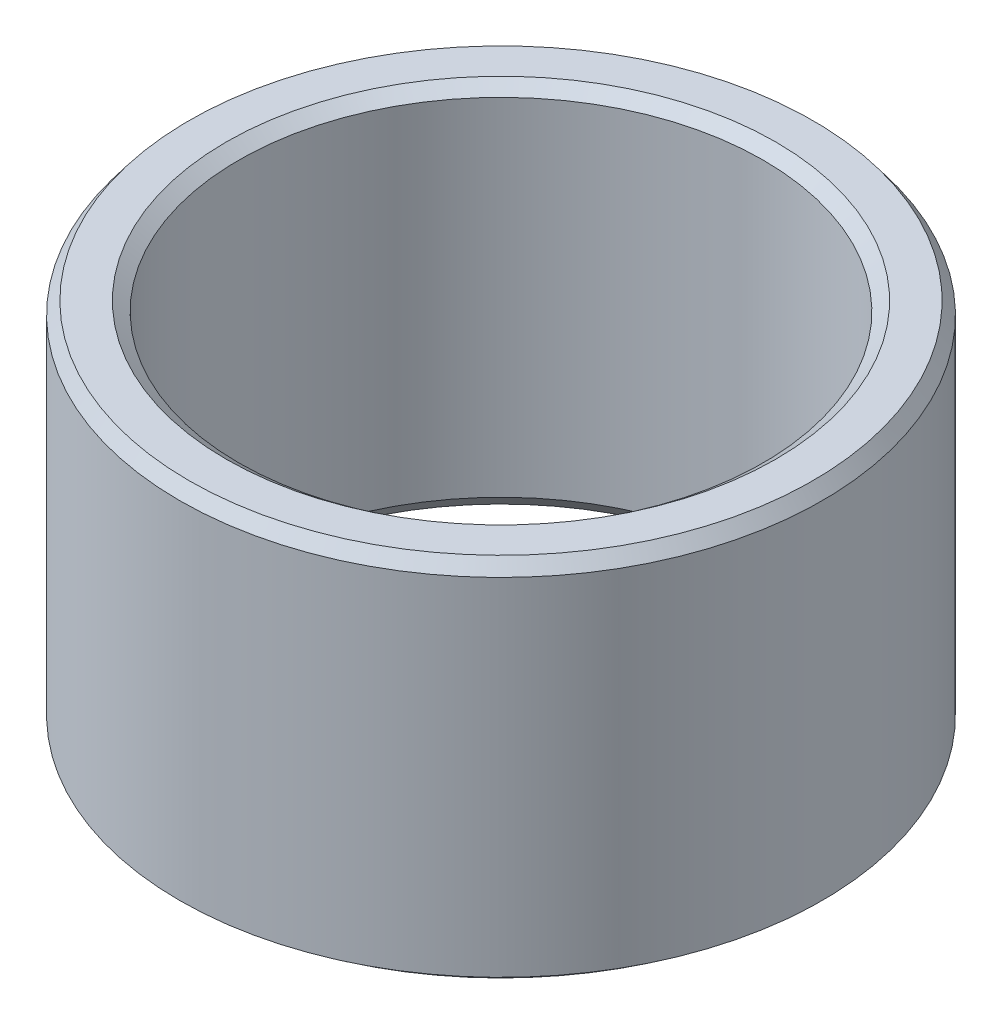
SolidWorks part; units mm, degrees
ref_plane "Front Plane" through (0, 0, 0) normal (0, 0, 1) x (1, 0, 0)
ref_plane "Top Plane" through (0, 0, 0) normal (0, 1, 0) x (1, 0, 0)
ref_plane "Right Plane" through (0, 0, 0) normal (1, 0, 0) x (0, 0, -1)
sketch "Sketch1" plane through (0, 0, 0) normal (0, 1, 0) x (1, 0, 0)
  circle A0 centre (0, 0) radius 55
  dimension "SLEEVE_OD" = 110
extrude "Boss-Extrude1" add sketch "Sketch1" along normal blind 63.0334
sketch "Sketch2" plane through (0, 0, 0) normal (0, 1, 0) x (1, 0, 0)
  circle A0 centre (0, 0) radius 44.8837
  dimension "BORE_D" = 89.7674
extrude "Cut-Extrude1" cut sketch "Sketch2" along normal through all
chamfer "Chamfer1" distance 2.148 angle 36.889 4 edges at (0, 63.0334, 44.8837) (0, 0, 44.8837) (0, 0, 55) (0, 63.0334, 55) first distance on face at (0, 63.0334, 44.8837) first distance on face at (0, 0, 44.8837) first distance on face at (0, 63.0334, 55)
